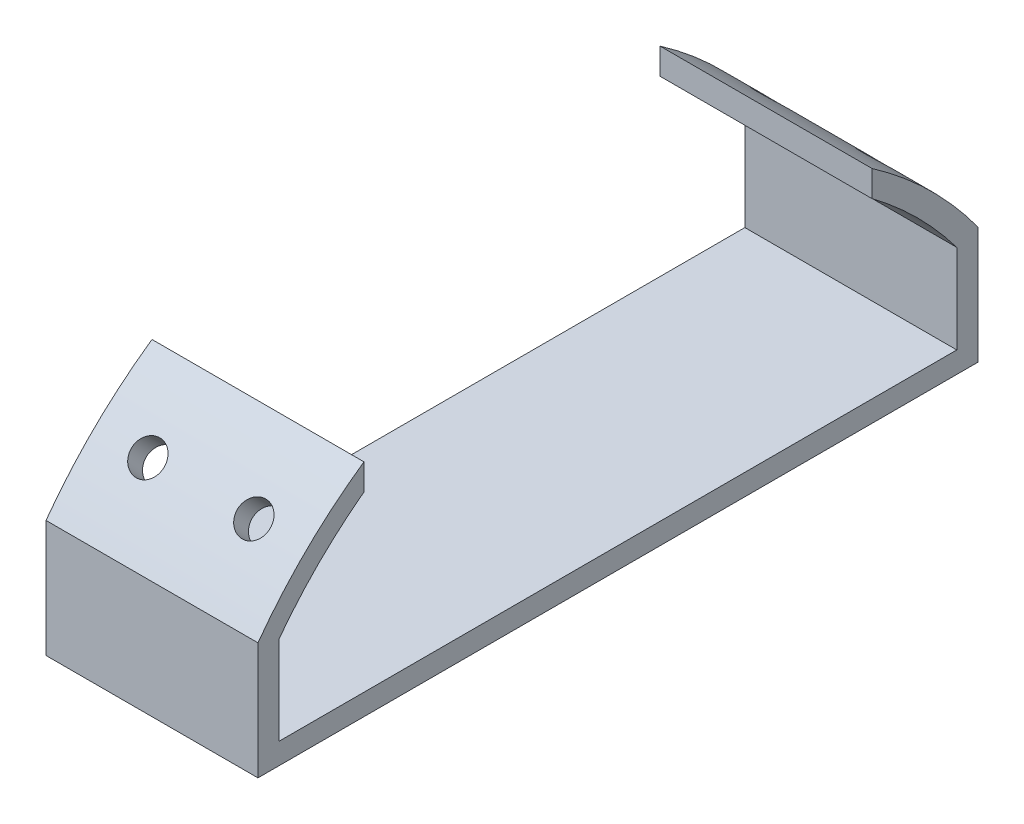
SolidWorks part; units mm, degrees
material "Alliage 1060"
ref_plane "Plan de face" through (0, 0, 0) normal (0, 0, 1) x (1, 0, 0)
ref_plane "Plan de dessus" through (0, 0, 0) normal (0, 1, 0) x (1, 0, 0)
ref_plane "Plan de droite" through (0, 0, 0) normal (1, 0, 0) x (0, 0, -1)
sketch "Esquisse1" plane through (0, 0, 0) normal (1, 0, 0) x (0, 0, -1)
  line L0 (-42, 0) -> (42, 0) construction
  line L1 (-38.9713, 15.66) -> (38.9713, 15.66) construction
  line L2 (-31.97, 24.0399) -> (-31.97, 15.66)
  line L3 (-33.97, 13.66) -> (33.97, 13.66)
  line L4 (-31.97, 15.66) -> (31.97, 15.66)
  line L5 (-23.97, 32.0225) -> (-23.97, 34.4882)
  line L6 (0, 56.4269) -> (0, -25.8363) construction
  line L7 (-33.97, 13.66) -> (-33.97, 24.699)
  line L8 (0, 0) -> (39.4833, 40.3273) construction
  line L9 (33.97, 13.66) -> (33.97, 24.699)
  line L10 (23.97, 32.0225) -> (23.97, 34.4882)
  line L11 (31.97, 24.0399) -> (31.97, 15.66)
  circle A0 centre (0, 0) radius 42 construction
  arc A1 (-33.97, 24.699) -> (-23.97, 34.4882) centre (0, 0) cw
  arc A2 (-31.97, 24.0399) -> (-23.97, 32.0225) centre (0, 0) cw
  arc A3 (31.97, 24.0399) -> (23.97, 32.0225) centre (0, 0) ccw
  arc A4 (33.97, 24.699) -> (23.97, 34.4882) centre (0, 0) ccw
  point P11 (-23.97, 33.2554)
  dimension "D1" = 84
  dimension "D5" = 40
  dimension "D6" = 10
  dimension "D2" = 15.66
  dimension "D3" = 31.97
  dimension "D4" = 2
  dimension "D7" = 2
  dimension "D8" = 7
extrude "Boss.-Extru.1" add sketch "Esquisse1" along normal blind 20
hole_wizard "Dégagement M2.51" positions "Esquisse3D2" profile "Esquisse3" hole size "M2.5" standard "ISO" end condition up to next
sketch3d "Esquisse3D2"
  line L0 (20, 34.4882, -23.97) -> (0, 34.4882, -23.97) construction
  point P0 (15, 30.0281, -29.3651)
  point P2 (5, 30.0281, -29.3651)
  dimension "D1" = 7
  dimension "D2" = 7
  dimension "D3" = 5
  dimension "D4" = 10
sketch "Esquisse3" plane through (15, 30.0281, -29.3651) normal (1, 0, 0) x (0, 0.6992, 0.715)
  line L0 (0, 0) -> (0, 22.8939)
  line L1 (0, 22.8939) -> (1.55, 22.8939)
  line L2 (1.55, 22.8939) -> (1.55, 0)
  line L5 (1.55, 0) -> (0, 0)
  line L11 (0, -6.35) -> (0, 107.95) construction
  dimension "Diamètre du perçage jusqu'au prochain" = 3.1
  dimension "Profondeur du perçage jusqu'au prochain" = 22.8939
mirror "Symétrie1" about plane through (0, 0, 0) normal (0, 0, 1) of "Dégagement M2.51"
